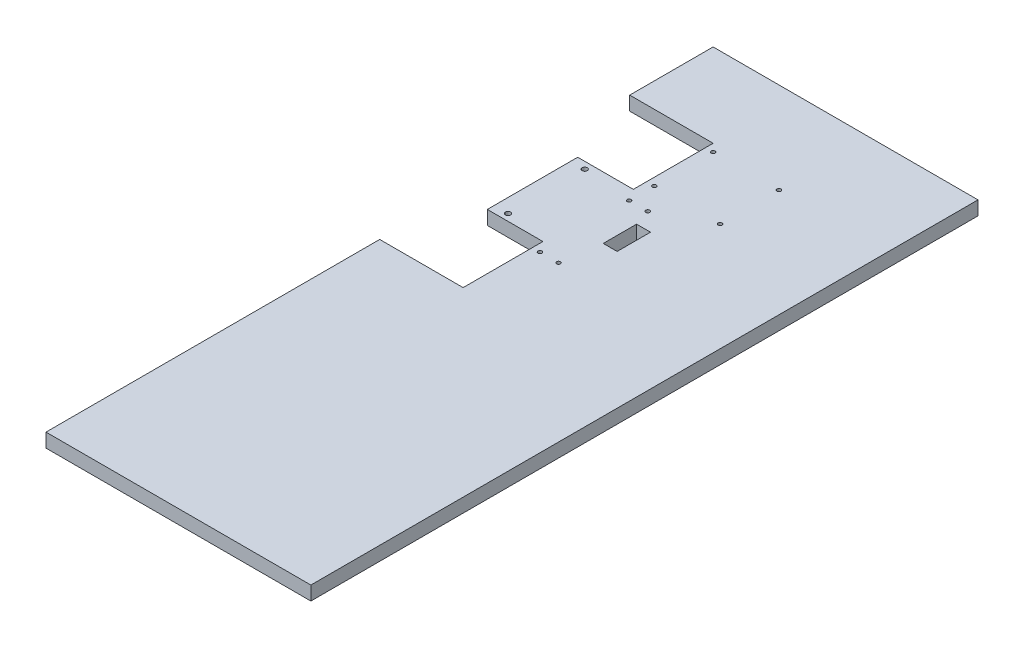
SolidWorks part; units mm, degrees
ref_plane "Front Plane" through (0, 0, 0) normal (0, 0, 1) x (1, 0, 0)
ref_plane "Top Plane" through (0, 0, 0) normal (0, 1, 0) x (1, 0, 0)
ref_plane "Right Plane" through (0, 0, 0) normal (1, 0, 0) x (0, 0, -1)
sketch "Sketch1" plane through (0, 0, 0) normal (0, 1, 0) x (1, 0, 0)
  line L0 (-147.6422, 18.3147) -> (-147.6422, -22.9603)
  line L1 (-160.3422, 92.8637) -> (-39.3795, 92.8637)
  line L2 (-122.2422, 54.7637) -> (-160.3422, 54.7637)
  line L3 (-39.3795, 92.8637) -> (-39.3795, -211.8093)
  line L4 (-39.3795, -211.8093) -> (-160.3422, -211.8093)
  line L5 (-160.3422, 54.7637) -> (-160.3422, 92.8637)
  line L7 (-147.6422, 18.3147) -> (-122.2422, 18.3147)
  line L8 (-122.2422, 54.7637) -> (-122.2422, 18.3147)
  line L9 (-147.6422, -22.9603) -> (-122.2422, -22.9603)
  line L10 (-107.7247, -9.9428) -> (-101.3747, -9.9428)
  line L11 (-160.3422, -211.8093) -> (-160.3422, -59.4093)
  line L12 (-122.2422, -22.9603) -> (-122.2422, -59.4093)
  line L13 (-160.3422, -59.4093) -> (-122.2422, -59.4093)
  line L14 (-107.7247, -9.9428) -> (-107.7247, 5.2972)
  line L15 (-107.7247, 5.2972) -> (-101.3747, 5.2972)
  line L16 (-101.3747, -9.9428) -> (-101.3747, 5.2972)
  line L17 (-107.7247, -9.9428) -> (-101.3747, 5.2972) construction
  line L18 (-107.7247, 5.2972) -> (-101.3747, -9.9428) construction
  circle A0 centre (-118.7497, -27.8153) radius 0.889
  circle A1 centre (-118.7497, 12.9197) radius 0.889
  circle A2 centre (-110.2647, 12.9197) radius 0.889
  circle A3 centre (-110.2647, -27.8153) radius 0.889
  circle A4 centre (-118.7497, 51.2712) radius 0.889
  circle A5 centre (-118.7497, 24.398) radius 0.889
  circle A6 centre (-88.7015, 51.2712) radius 0.889
  circle A7 centre (-88.7015, 24.398) radius 0.889
  point P14 (-104.5497, -2.3228)
  dimension "D9" = 1.778
  dimension "D10" = 1.778
  dimension "D11" = 3.4925
  dimension "D12" = 3.4925
  dimension "D14" = 4.855
  dimension "D21" = 3.4925
  dimension "D22" = 3.4925
  dimension "D23" = 26.8732
  dimension "D24" = 30.0482
  dimension "D1" = 41.275
  dimension "D2" = 25.4
  dimension "D3" = 25.4
  dimension "D4" = 36.449
  dimension "D5" = 36.449
  dimension "D6" = 38.1
  dimension "D7" = 38.1
  dimension "D8" = 38.1
  dimension "D13" = 5.395
  dimension "D16" = 2.54
  dimension "D17" = 15.24
  dimension "D18" = 20.6375
  dimension "D19" = 6.35
  dimension "D20" = 152.4
  dimension "D15" = 2
extrude "Boss-Extrude1" add sketch "Sketch1" along normal blind 6.35
sketch "Sketch2" plane through (0, 6.35, 0) normal (0, 1, 0) x (1, 0, 0)
  line L0 (-147.6422, 18.3147) -> (-147.6422, -22.9603) construction
  circle A0 centre (-141.2922, 15.1772) radius 1.1684
  circle A1 centre (-141.2922, -19.8228) radius 1.1684
  point P6 (-147.6422, -2.3228)
  point P7 (-147.6422, -2.3228)
  dimension "D1" = 2.3368
  dimension "D2" = 2.3368
  dimension "D3" = 6.35
  dimension "D4" = 6.35
  dimension "D5" = 17.5
  dimension "D6" = 17.5
extrude "Cut-Extrude1" cut sketch "Sketch2" against normal blind 6.35
